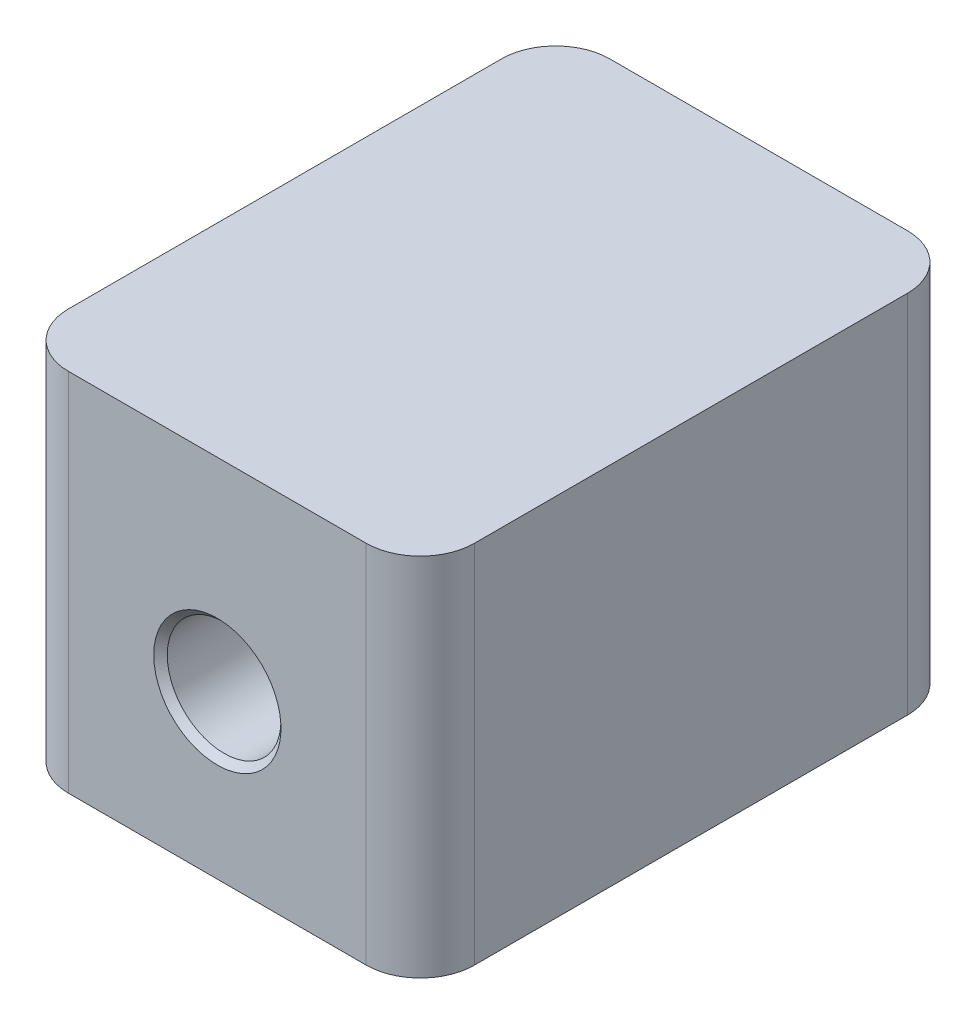
SolidWorks part; units mm, degrees
material "Brass"
ref_plane "Front" through (0, 0, 0) normal (0, 0, 1) x (1, 0, 0)
ref_plane "Top" through (0, 0, 0) normal (0, 1, 0) x (1, 0, 0)
ref_plane "Right" through (0, 0, 0) normal (1, 0, 0) x (0, 0, -1)
ref_axis "X-Axis" through (-80.9, 0, 0) along (1, 0, 0)
ref_axis "Y-Axis" through (0, -50, 0) along (0, 1, 0)
ref_axis "Z-Axis" through (0, 0, -80.9) along (0, 0, 1)
sketch "Sketch1" plane through (0, 0, 0) normal (0, 0, 1) x (1, 0, 0)
  line L1 (-7.5, -6) -> (7.5, -6)
  line L2 (-7.5, -6) -> (-7.5, 7.5)
  line L3 (-7.5, 7.5) -> (7.5, 7.5)
  line L4 (7.5, -6) -> (7.5, 7.5)
  line L5 (-7.5, -6) -> (7.5, 7.5) construction
  line L6 (-7.5, 7.5) -> (7.5, -6) construction
  point P0 (0, 0.75)
  dimension "D1" = 15
  dimension "D2" = 13.5
  dimension "D3" = 7.5
extrude "Boss-Extrude1" add sketch "Sketch1" along normal mid plane 20
fillet "Fillet1" radius 2 4 edges at (-7.5, 0.75, -10) (7.5, 0.75, -10) (7.5, 0.75, 10) (-7.5, 0.75, 10)
hole_wizard "M5 Ports" positions "3DSketch1" profile "Sketch2" hole size "M5x0.8" standard "ANSI Metric"
sketch3d "3DSketch1"
  point P0 (0, 0, 10)
  point P2 (0, 0, -10)
sketch "Sketch2" plane through (0, 0, 10) normal (1, 0, 0) x (0, -1, 0)
  line L0 (0, 0) -> (0, 5)
  line L1 (0, 5) -> (2.1, 5)
  line L2 (2.1, 5) -> (2.1, 0)
  line L5 (2.1, 0) -> (0, 0)
  line L10 (0, 5) -> (-2.1, 5) construction
  line L11 (0, -6.35) -> (0, 107.95) construction
  dimension "Hole Dia." = 4.2
  dimension "Hole Depth" = 5
  dimension "Drill Angle" = 180
chamfer "M5 Port Chamfer" distance 0.25 angle 45 2 edges at (-2.1, 0, -10) (2.1, 0, 10)
sketch "Sketch3" plane through (0, -6, 0) normal (0, -1, 0) x (1, 0, 0)
  line L0 (-5.5, 0) -> (5.5, 0) construction
  circle A0 centre (-5.5, 0) radius 1.25
  circle A1 centre (5.5, 0) radius 1.25
  dimension "D1" = 2.5
  dimension "D2" = 11
extrude "Cut-Extrude1" cut sketch "Sketch3" against normal blind 4
chamfer "Chamfer2" distance 0.15 angle 45 2 edges at (5.5, -6, -1.25) (-5.5, -6, -1.25)
move or copy body "Body-Move/Copy2" [suppressed] bodies to move or copy 103
move or copy body "Body-Move/Copy1" [suppressed] bodies to move or copy 103
